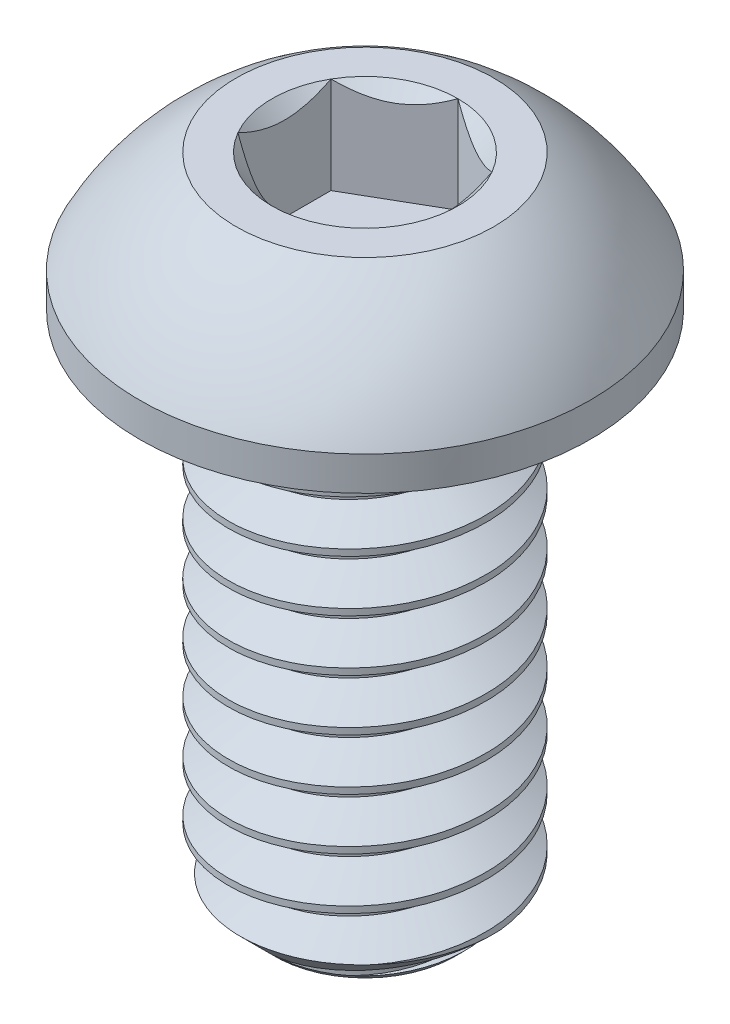
SolidWorks part; units mm, degrees
ref_plane "Front Plane" through (0, 0, 0) normal (0, 0, 1) x (1, 0, 0)
ref_plane "Top Plane" through (0, 0, 0) normal (0, 1, 0) x (1, 0, 0)
ref_plane "Right Plane" through (0, 0, 0) normal (1, 0, 0) x (0, 0, -1)
sketch "Sketch1" plane through (0, 0, 0) normal (0, 1, 0) x (1, 0, 0)
  circle A0 centre (0, 0) radius 3.175
  point P3 (-3.175, 0)
  point P4 (3.175, 0)
  dimension "D1" = 6.35
extrude "Boss-Extrude1" add sketch "Sketch1" against normal blind 12.7
sketch "Sketch2" plane through (0, -12.7, 0) normal (0, -1, 0) x (1, 0, 0)
  circle A1 centre (0, 0) radius 3.175
  circle A2 centre (0, 0) radius 3.175
  point P0 (0, -3.175)
  dimension "D1" = 0
curve "Helix/Spiral1" pitch 1.27 height 13.97 turns 11
sketch "Sketch3" plane through (0, 0, 0) normal (1, 0, 0) x (0, 0, -1)
  line L0 (3.3125, -12.6206) -> (2.2126, -13.2556) construction
  line L1 (2.2126, -13.2556) -> (3.3125, -13.8906) construction
  line L2 (3.3125, -13.8906) -> (3.3125, -12.6206) construction
  line L3 (2.3501, -13.1762) -> (2.3501, -13.335) construction
  line L4 (3.175, -12.7) -> (3.175, -13.8112) construction
  line L5 (2.2126, -13.2556) -> (2.3501, -13.2556) construction
  line L6 (3.175, -13.2556) -> (3.3125, -13.2556) construction
  line L8 (2.2126, -13.2556) -> (-3.175, -13.2556) construction
  line L9 (2.3501, -13.1762) -> (3.2437, -12.6603)
  line L10 (2.3501, -13.1762) -> (2.3501, -13.335)
  line L11 (2.3501, -13.335) -> (3.2437, -13.8509)
  line L12 (3.2437, -13.8509) -> (3.2437, -12.6603)
  line L14 (-3.175, -13.2556) -> (-3.175, -11.9856) construction
  line L15 (-3.175, -11.9856) -> (-3.175, -10.7156) construction
  line L16 (-3.175, -10.7156) -> (-3.175, -9.4456) construction
  line L17 (-3.175, -9.4456) -> (-3.175, -8.1756) construction
  line L18 (-3.175, 0) -> (-3.175, -12.7) construction
  point P15 (3.2437, -13.2556)
  dimension "D1" = 1.27
  dimension "D2" = 0.1588
sweep "Cut-Sweep1" cut profiles "Sketch3" path "Helix/Spiral1" align with end faces yes
sketch "Sketch4" plane through (0, -12.7, 0) normal (0, -1, 0) x (1, 0, 0)
  circle A0 centre (0, 0) radius 2.2126
extrude "Cut-Extrude1" cut sketch "Sketch4" against normal blind 1.27 draft 45 flip side to cut
sketch "Sketch5" plane through (0, 0, 0) normal (0, 0, 1) x (1, 0, 0)
  line L0 (0, 0) -> (0, 3.3528)
  line L1 (-5.5499, 0) -> (0, 0)
  line L2 (0, 3.3528) -> (-3.175, 3.3528)
  line L4 (-5.5499, 0.8382) -> (-5.5499, 0)
  line L5 (0, 0) -> (0, -12.7) construction
  arc A0 (-3.175, 3.3528) -> (-5.5499, 0.8382) centre (0, -2.0246) ccw
  dimension "D1" = 3.3528
  dimension "D2" = 0.8382
  dimension "D4" = 11.0998
revolve "Revolve1" add sketch "Sketch5" angle 360 mid plane about L0
sketch "Sketch6" plane through (0, 3.3528, 0) normal (0, 1, 0) x (1, 0, 0)
  line L1 (0, 2.2914) -> (-1.9844, 1.1457)
  line L2 (-1.9844, 1.1457) -> (-1.9844, -1.1457)
  line L3 (-1.9844, -1.1457) -> (0, -2.2914)
  line L4 (0, -2.2914) -> (1.9844, -1.1457)
  line L5 (1.9844, -1.1457) -> (1.9844, 1.1457)
  line L6 (1.9844, 1.1457) -> (0, 2.2914)
  circle A0 centre (0, 0) radius 1.9844 construction
  dimension "D1" = 3.9688
extrude "Cut-Extrude2" cut sketch "Sketch6" against normal blind 2.3813
sketch "Sketch7" plane through (0, 3.3528, 0) normal (0, 1, 0) x (1, 0, 0)
  circle A0 centre (0, 0) radius 2.2914
extrude "Cut-Extrude3" cut sketch "Sketch7" against normal blind 2.3813 draft 45
sketch "SketchZ" plane through (0, 0, 0) normal (0, 0, 1) x (1, 0, 0)
  line L0 (3.175, -12.9381) -> (3.175, -11.6681) construction
  line L2 (0, -13.2556) -> (0, -11.9856) construction
  line L4 (3.175, -12.9381) -> (0, -12.9381) construction
  line L5 (0, -9.4456) -> (0, -8.1756) construction
  line L6 (0, -12.6206) -> (0, -13.2556) construction
equation "\"D3@Helix/Spiral1\" = \"D4@Helix/Spiral1\" + \"D1@Boss-Extrude1\""
equation "\"D1@Sketch3\" = \"D4@Helix/Spiral1\""
equation "\"D2@Sketch3\" = \"D1@Sketch3\" / 8"
equation "\"D1@Cut-Extrude1\" = \"D4@Helix/Spiral1\""
equation "\"D1@Cut-Extrude2\" = \"D1@Sketch6\" * 3/5"
equation "\"D1@Cut-Extrude3\" = \"D1@Cut-Extrude2\""
equation "\"D2@Sketch5\" = \"D1@Sketch5\" * 1/4"
